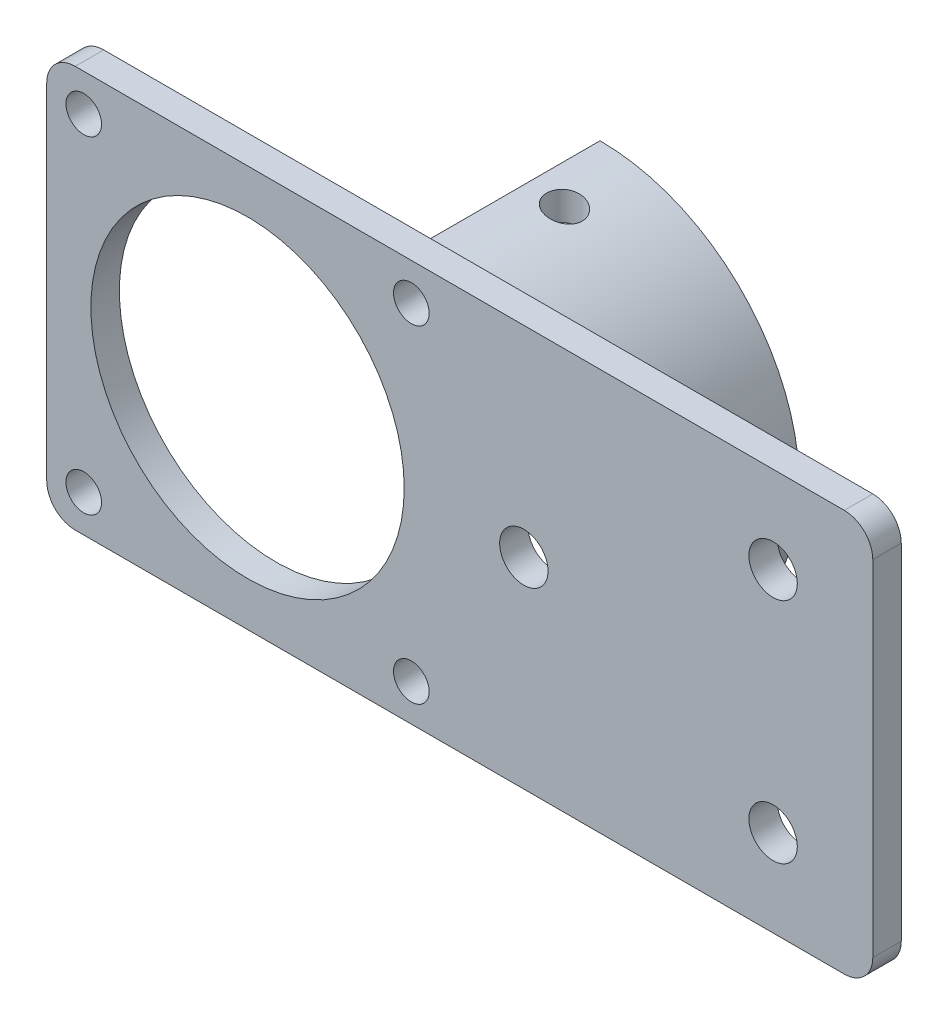
SolidWorks part; units mm, degrees
ref_plane "Front Plane" through (0, 0, 0) normal (0, 0, 1) x (1, 0, 0)
ref_plane "Top Plane" through (0, 0, 0) normal (0, 1, 0) x (1, 0, 0)
ref_plane "Right Plane" through (0, 0, 0) normal (1, 0, 0) x (0, 0, -1)
sketch "Sketch1" plane through (0, 0, 0) normal (0, 0, 1) x (1, 0, 0)
  line L0 (0, 14) -> (0, -14)
  arc A0 (0, -14) -> (0, 14) centre (0, 0) ccw
  dimension "D1" = 28
  dimension "D2" = 28
extrude "Boss-Extrude1" add sketch "Sketch1" along normal blind 12
sketch "Sketch2" plane through (0, 0, 12) normal (0, 0, 1) x (1, 0, 0)
  line L0 (-34.1826, 0) -> (45.237, 0) construction
  line L1 (3.35, 26.155) -> (3.35, -23.0665) construction
  line L2 (0, 14) -> (0, -14) construction
  line L3 (-24.85, 14.1) -> (-24.85, -14.1)
  line L4 (-24.85, 14.1) -> (33.15, 14.1)
  line L5 (33.15, 14.1) -> (33.15, -14.1)
  line L6 (33.15, -14.1) -> (-24.85, -14.1)
  point P10 (-24.85, 0)
  dimension "D1" = 3.35
  dimension "D2" = 28.2
  dimension "D3" = 24.85
  dimension "D4" = 28.2
  dimension "D5" = 58
  dimension "D6" = 58
  dimension "D7" = 28.2
extrude "Boss-Extrude2" add sketch "Sketch2" along normal blind 2
shell "Shell2" thickness 2 removed face at (0, 0, 6)
sketch "Sketch3" plane through (0, 0, 14) normal (0, 0, 1) x (1, 0, 0)
  line L0 (-35.7582, 0) -> (48.1355, 0) construction
  line L1 (3.35, 17.8195) -> (3.35, -18.9781) construction
  line L2 (-24.85, 14.1) -> (-24.85, -14.1) construction
  line L3 (-10.75, 19.3756) -> (-10.75, -18.9781) construction
  circle A0 centre (-10.75, 0) radius 11
  circle A1 centre (-22.25, 11.5) radius 1.25
  circle A2 centre (-22.25, -11.5) radius 1.25
  circle A3 centre (0.75, -11.5) radius 1.25
  circle A4 centre (0.75, 11.5) radius 1.25
  dimension "D4" = 22
  dimension "D5" = 2.5
  dimension "D6" = 2.5
  dimension "D1" = 3.35
  dimension "D2" = 14.1
  dimension "D3" = 14.1
  dimension "D7" = 11.5
  dimension "D8" = 11.5
  dimension "D9" = 11.5
  dimension "D10" = 11.5
extrude "Cut-Extrude1" cut sketch "Sketch3" against normal blind 2
fillet "Fillet1" radius 2 4 edges at (33.15, 14.1, 13) (33.15, -14.1, 13) (-24.85, -14.1, 13) (-24.85, 14.1, 13)
sketch "Sketch4" plane through (0, 0, 14) normal (0, 0, 1) x (1, 0, 0)
  line L0 (45.2065, 0) -> (-43.5133, 0) construction
  line L1 (33.15, -12.1) -> (33.15, 12.1) construction
  circle A0 centre (26.15, 8) radius 1.7
  circle A1 centre (26.15, -8) radius 1.7
  circle A2 centre (8.65, 0) radius 1.7
  dimension "D1" = 3.4
  dimension "D2" = 3.4
  dimension "D3" = 3.4
  dimension "D4" = 8
  dimension "D5" = 8
  dimension "D6" = 7
  dimension "D7" = 7
  dimension "D8" = 24.5
extrude "Cut-Extrude2" cut sketch "Sketch4" against normal blind 2
sketch "Sketch5" plane through (0, 0, 0) normal (0, 0, -1) x (-1, 0, 0)
  line L0 (-38.9797, 0) -> (38.9701, 0) construction
  line L1 (0, 14) -> (0, -14) construction
  circle A0 centre (-5, -9) radius 1.7
  circle A1 centre (-5, 9) radius 1.7
  dimension "D1" = 3.4
  dimension "D2" = 3.4
  dimension "D3" = 9
  dimension "D4" = 9
  dimension "D5" = 5
  dimension "D6" = 5
extrude "Cut-Extrude3" cut sketch "Sketch5" against normal blind 2
sketch "Sketch7" plane through (0, 0, 0) normal (1, 0, 0) x (0, 0, -1)
  line L0 (16.8215, 0) -> (-36.6979, 0) construction
  line L1 (0, 14) -> (0, -14) construction
  circle A0 centre (-5, 0) radius 1.25
  dimension "D1" = 2.5
  dimension "D2" = 5
extrude "Cut-Extrude6" cut sketch "Sketch7" along normal blind 14
sketch "Sketch8" plane through (0, 0, 0) normal (0, 1, 0) x (1, 0, 0)
  line L0 (0, 26.9646) -> (0, -55.8018) construction
  line L1 (14, 0) -> (0, 0) construction
  circle A0 centre (2.5, -5) radius 1.25
  dimension "D1" = 2.5
  dimension "D2" = 5
  dimension "D3" = 2.5
extrude "Cut-Extrude7" cut sketch "Sketch8" against normal mid plane 34
